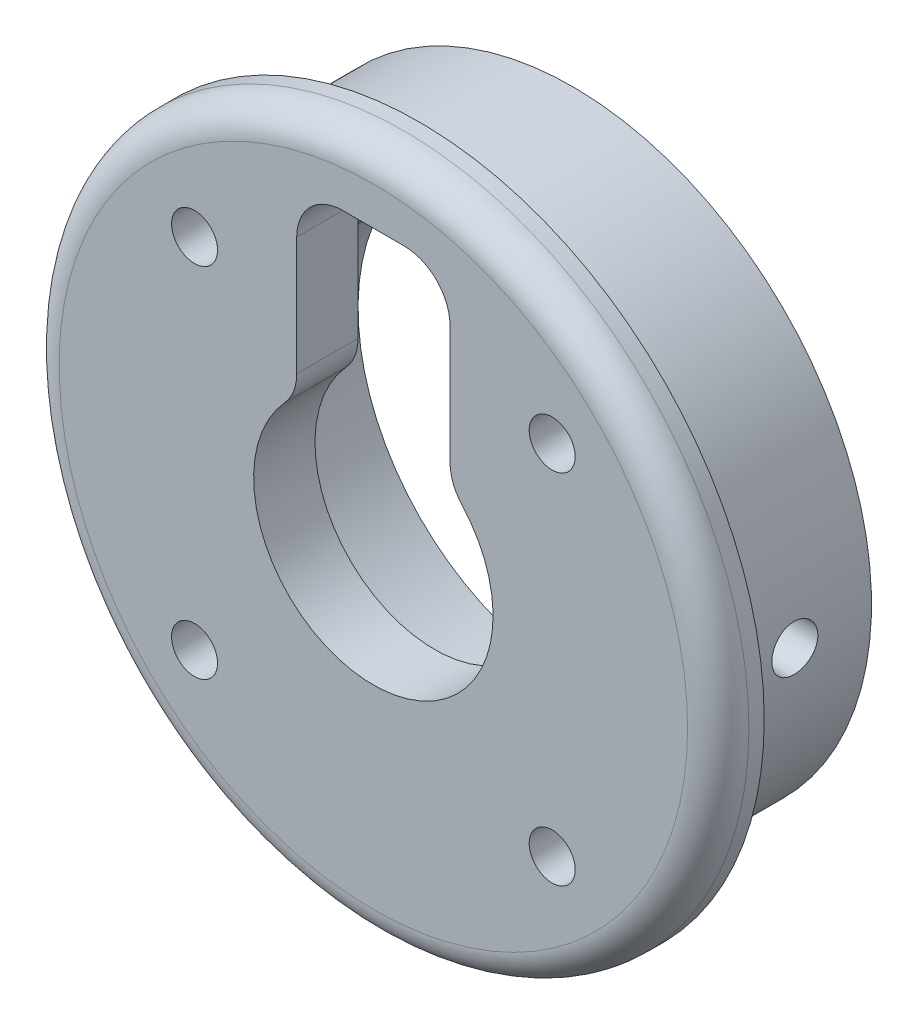
SolidWorks part; units mm, degrees
material "ABS"
ref_plane "Front Plane" through (0, 0, 0) normal (0, 0, 1) x (1, 0, 0)
ref_plane "Top Plane" through (0, 0, 0) normal (0, 1, 0) x (1, 0, 0)
ref_plane "Right Plane" through (0, 0, 0) normal (1, 0, 0) x (0, 0, -1)
sketch "Sketch1" plane through (0, 0, 0) normal (0, 0, 1) x (1, 0, 0)
  circle A2 centre (750, 29.3136) radius 22.5
extrude "Boss-Extrude1" add sketch "Sketch1" along normal blind 3
sketch "Sketch2" plane through (0, 0, 0) normal (0, 0, -1) x (-1, 0, 0)
  circle A2 centre (-750, 29.3136) radius 19.5
  circle A3 centre (-750, 29.3136) radius 19.5
  dimension "D1" = 3
extrude "Boss-Extrude2" add sketch "Sketch2" along normal blind 10
sketch "Sketch3" plane through (0, 0, 3) normal (0, 0, 1) x (1, 0, 0)
  line L0 (750, 6.8136) -> (750, 29.3136) construction
  line L1 (750, 29.3136) -> (772.5, 29.3136) construction
  line L2 (750, 29.3136) -> (761.6673, 17.6464) construction
  line L4 (748, 47.3136) -> (752, 47.3136)
  line L5 (745, 44.3136) -> (745, 35.3136)
  line L7 (755, 44.3136) -> (755, 35.3136)
  circle A0 centre (750, 29.3136) radius 16.5 construction
  circle A1 centre (750, 29.3136) radius 22.5 construction
  circle A2 centre (761.6673, 17.6464) radius 1.5
  circle A3 centre (738.3327, 17.6464) radius 1.5
  circle A4 centre (738.3327, 40.9809) radius 1.5
  circle A5 centre (761.6673, 40.9809) radius 1.5
  arc A6 (745, 35.3136) -> (755, 35.3136) centre (750, 29.3136) ccw
  arc A7 (752, 47.3136) -> (755, 44.3136) centre (752, 44.3136) cw
  arc A8 (748, 47.3136) -> (745, 44.3136) centre (748, 44.3136) ccw
  point P18 (750, 29.3136)
  point P22 (755, 47.3136)
  point P25 (745, 47.3136)
  dimension "D1" = 4
extrude "Cut-Extrude1" cut sketch "Sketch3" against normal up to surface (13 mm away) up to face at (730.5, 29.3136, -10)
sketch "Sketch4" plane through (745, 0, 0) normal (1, 0, 0) x (0, 0, -1)
  circle A0 centre (5, 29.3136) radius 1.5
extrude "Cut-Extrude2" cut sketch "Sketch4" against normal through all both and the other way through all
sketch "Sketch5" plane through (0, 0, -10) normal (0, 0, -1) x (-1, 0, 0)
  circle A0 centre (-750, 29.3136) radius 14
extrude "Cut-Extrude3" cut sketch "Sketch5" against normal blind 9
fillet "Fillet1" radius 3 4 edges at (755, 35.3136, 1) (745, 35.3136, 1) (755, 42.3903, -5.5) (745, 42.3903, -5.5)
fillet "Fillet2" radius 2 1 edges at (772.5, 29.3136, 3)
